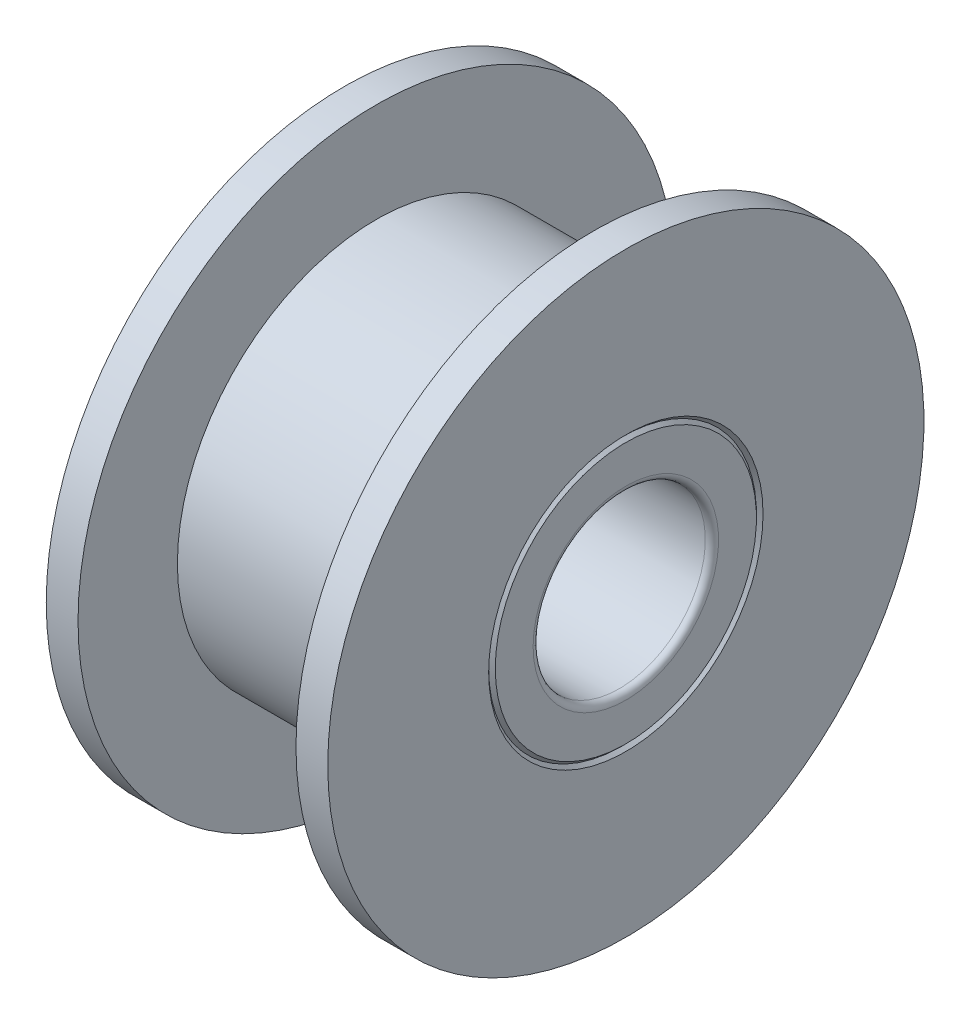
SolidWorks part; units mm, degrees
material "1.2311 (40CrMnMo7)"
ref_plane "Front" through (0, 0, 0) normal (0, 0, 1) x (1, 0, 0)
ref_plane "Top" through (0, 0, 0) normal (0, 1, 0) x (1, 0, 0)
ref_plane "Right" through (0, 0, 0) normal (1, 0, 0) x (0, 0, -1)
sketch "Sketch 1" plane through (0, 0, 0) normal (0, 0, 1) x (1, 0, 0)
  line L0 (5.5, 7.5) -> (5.5, 2.6424)
  line L1 (1, -1.5) -> (14, -1.5) construction
  line L2 (5.5, 7.5) -> (6.46, 7.5)
  line L4 (6.46, 4.5) -> (13.04, 4.5)
  line L5 (13.04, 4.5) -> (13.04, 7.5)
  line L6 (13.04, 7.5) -> (14, 7.5)
  line L7 (14, 1.1) -> (14, 2.4424)
  line L8 (14, 2.4424) -> (13.9, 2.5424)
  line L9 (13.9, 2.5424) -> (14, 2.6424)
  line L10 (14, 2.6424) -> (14, 7.5)
  line L11 (14, 1.1) -> (5.5, 1.1)
  line L12 (6.46, 7.5) -> (6.46, 4.5)
  line L14 (5.5, 2.3576) -> (5.6035, 2.5)
  line L15 (5.6035, 2.5) -> (5.5, 2.6424)
  line L16 (5.5, 2.3576) -> (5.5, 1.1)
  dimension "D1" = 6
  dimension "D2" = 0.96
  dimension "D3" = 2.6
  dimension "D4" = 8.5
  dimension "D5" = 0.1
  dimension "D6" = 5
  dimension "D7" = 9
revolve "Body" add sketch "Sketch 1" angle 360 about L1 region at (9.7506, 3.3324, 0)
sketch "Sketch 3" plane through (6.46, 0, 0) normal (1, 0, 0) x (0, 0, -1)
  line L0 (0, 0) -> (9.7637, 0) construction
  circle A18 centre (0, 5.855) radius 0.55
  point P45 (0, 0)
ref_axis "Axis1" through (-2.8, 0, 0) along (1, 0, 0)
fillet "Fillet1" radius 0.2 2 edges at (14, -1.5, 2.6) (5.5, -1.5, 2.6)
